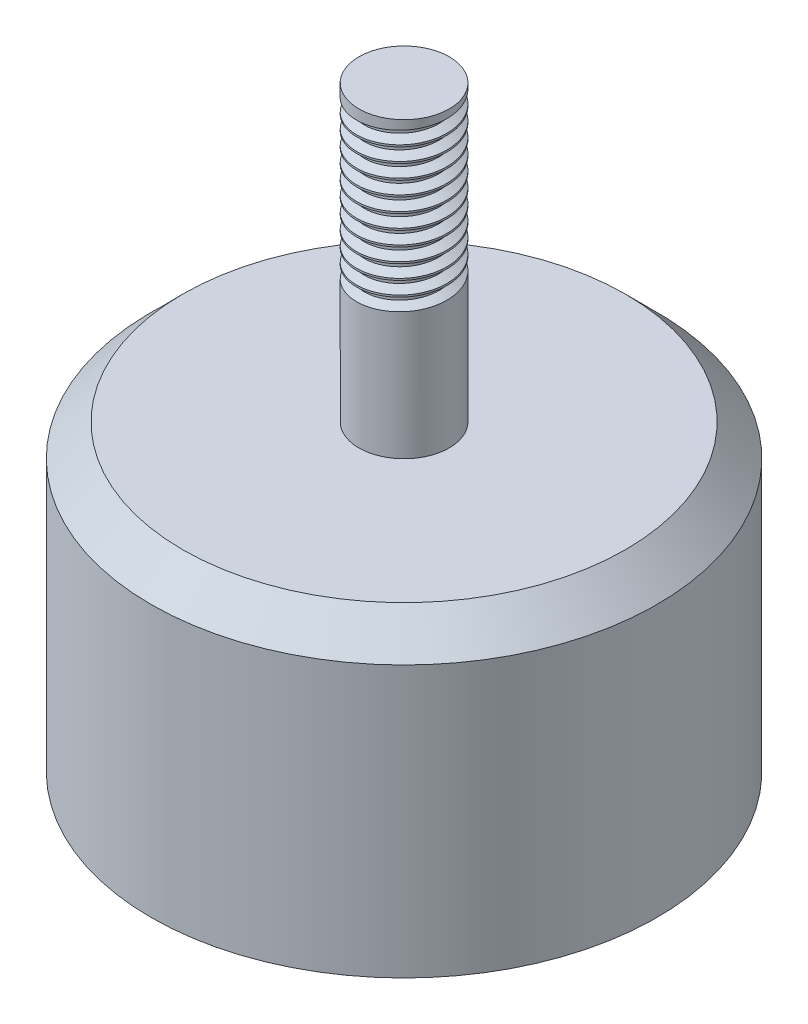
SolidWorks part; units mm, degrees
ref_plane "Front Plane" through (0, 0, 0) normal (0, 0, 1) x (1, 0, 0)
ref_plane "Top Plane" through (0, 0, 0) normal (0, 1, 0) x (1, 0, 0)
ref_plane "Right Plane" through (0, 0, 0) normal (1, 0, 0) x (0, 0, -1)
sketch "Sketch1" plane through (0, 0, 0) normal (0, 1, 0) x (1, 0, 0)
  circle A0 centre (0, 0) radius 14
  dimension "D1" = 28
extrude "Boss-Extrude1" add sketch "Sketch1" along normal blind 17.5
sketch "Sketch2" plane through (0, 17.5, 0) normal (0, 1, 0) x (1, 0, 0)
  circle A0 centre (0, 0) radius 6
  dimension "D1" = 12
extrude "Boss-Extrude2" add sketch "Sketch2" along normal blind 1.5
sketch "Sketch3" plane through (0, 19, 0) normal (0, 1, 0) x (1, 0, 0)
  circle A0 centre (0, 0) radius 2.5
  dimension "D1" = 5
extrude "Boss-Extrude3" add sketch "Sketch3" along normal blind 14
thread "Thread1" pitch 0.8 method cut profile "Thread Profile1" start angle 0, offset 0, length 9, pitch 0.8, diameter 5
ref_plane "Plane1" through (-2.5, 33, 0) normal (0, 0, 1) x (-1, 0, 0)
sketch "Thread Profile1" plane through (-2.5, 33, 0) normal (0, 0, 1) x (-1, 0, 0)
  line L0 (0, 0) -> (0, 0.8) construction
  line L11 (0, 0) -> (0, 0.7)
  line L12 (0, 0.7) -> (-0.433, 0.45)
  line L13 (-0.433, 0.45) -> (-0.433, 0.25)
  line L15 (-0.433, 0.25) -> (0, 0)
  line L17 (-0.433, 0.35) -> (0, 0.35) construction
  point P2 (0, 0)
  dimension "Pitch" = 0.8
  dimension "Profile_Angle" = 60
  dimension "Profile_Land" = 0.2
  dimension "Profile_Height" = 0.433
chamfer "Chamfer1" distance 2.5 angle 45 1 edges at (0, 17.5, 14)
sketch "Sketch8" plane through (0, 0, 0) normal (0, -1, 0) x (1, 0, 0)
  line L0 (8, 0) -> (-8, 0) construction
  line L1 (0, -9.5) -> (0, 9.5) construction
  circle A0 centre (0, 0) radius 9.5 construction
  circle A1 centre (0, 0) radius 8 construction
  dimension "D1" = 19
  dimension "D2" = 16
hole_wizard "M3x0.5 Tapped Hole1" positions "Sketch9" profile "Sketch10" tap size "M3x0.5" standard "ANSI Metric"
sketch "Sketch9" plane through (0, 0, 0) normal (0, -1, 0) x (-1, 0, 0)
  point P0 (0, 9.5)
  point P3 (-8, 0)
  point P6 (0, -9.5)
  point P9 (8, 0)
sketch "Sketch10" plane through (0, 0, -9.5) normal (1, 0, 0) x (0, 0, -1)
  line L0 (0, 0) -> (0, 5)
  line L1 (0, 5) -> (1.25, 4.2489)
  line L2 (1.25, 4.2489) -> (1.25, 0.3164)
  line L3 (1.25, 0.3164) -> (1.525, 0)
  line L5 (1.525, 0) -> (0, 0)
  line L6 (-1.25, 0.3164) -> (-1.525, 0) construction
  line L10 (0, 5) -> (-1.25, 4.2489) construction
  line L11 (0, -6.35) -> (0, 107.95) construction
  dimension "Tap Drill Dia." = 2.5
  dimension "Tap Drill Depth" = 5
  dimension "Near C'Sink Dia." = 3.05
  dimension "Near C'Sink Angle" = 82
  dimension "Drill Angle" = 118
cosmetic thread "Hole Thread1" parameters "D1"=6, "D2"=3
cosmetic thread "Hole Thread2" parameters "D1"=6, "D2"=3
cosmetic thread "Hole Thread3" parameters "D1"=6, "D2"=3
cosmetic thread "Hole Thread4" parameters "D1"=6, "D2"=3
sketch "Sketch11" plane through (0, 19, 0) normal (0, 1, 0) x (1, 0, 0)
  circle A0 centre (0, 0) radius 14
  circle A1 centre (0, 0) radius 2.5
  circle A2 centre (0, 0) radius 2.5 construction
  circle A3 centre (0, 0) radius 14 construction
extrude "Cut-Extrude1" cut sketch "Sketch11" against normal blind 2.25
sketch "Sketch12" plane through (0, 0, 0) normal (0, -1, 0) x (1, 0, 0)
  circle A0 centre (0, 0) radius 3.25
  dimension "D1" = 6.5
extrude "Boss-Extrude4" add sketch "Sketch12" along normal blind 2
